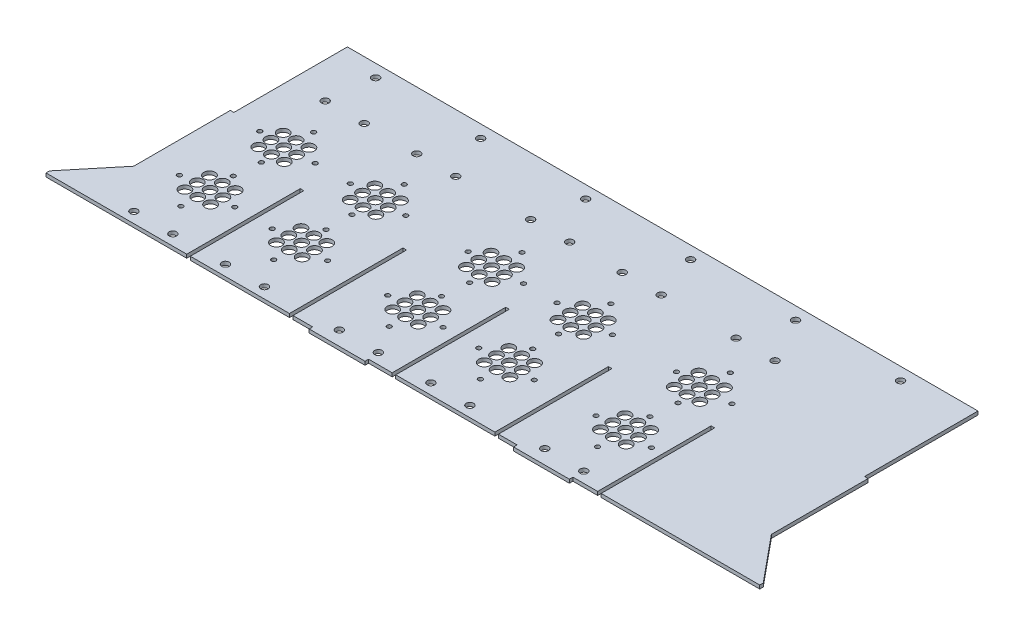
SolidWorks part; units mm, degrees
material "6061-T6 (SS)"
ref_plane "X-Y Datum" through (0, 0, 0) normal (0, 0, 1) x (1, 0, 0)
ref_plane "X-Z Datum" through (0, 0, 0) normal (0, 1, 0) x (1, 0, 0)
ref_plane "Y-Z Datum" through (0, 0, 0) normal (1, 0, 0) x (0, 0, -1)
sketch "Sketch1" plane through (0, 0, 0) normal (0, 0, 1) x (1, 0, 0)
  line L1 (-285.4305, -1.5875) -> (285.4305, -1.5875)
  line L2 (-285.4305, -1.5875) -> (-285.4305, 1.5875)
  line L3 (-285.4305, 1.5875) -> (285.4305, 1.5875)
  line L4 (285.4305, -1.5875) -> (285.4305, 1.5875)
  line L5 (-285.4305, -1.5875) -> (285.4305, 1.5875) construction
  line L6 (-285.4305, 1.5875) -> (285.4305, -1.5875) construction
  point P0 (0, 0)
  dimension "D1" = 570.861
  dimension "D2" = 3.175
extrude "Boss-Extrude1" add sketch "Sketch1" along normal blind 232.6
sketch "Sketch2" plane through (0, 1.5875, 0) normal (0, 1, 0) x (1, 0, 0)
  line L0 (-176.5505, -181.8) -> (-285.4305, -181.8) construction
  line L1 (-285.4305, -232.6) -> (-285.4305, 0) construction
  line L3 (285.4305, -232.6) -> (-285.4305, -232.6) construction
  line L4 (-178.0615, -232.6) -> (-174.8865, -232.6)
  line L6 (-178.0615, -118.3) -> (-174.8865, -118.3)
  line L8 (-178.0615, -232.6) -> (-174.8865, -232.6)
  line L9 (-178.0615, -232.6) -> (-178.0615, -118.3)
  line L10 (-178.0615, -118.3) -> (-174.8865, -118.3)
  line L11 (-174.8865, -232.6) -> (-174.8865, -118.3)
  line L17 (-178.0615, -118.3) -> (-174.8865, -118.3)
  line L38 (-285.4305, 0) -> (-282.2555, 0)
  line L39 (-285.4305, 0) -> (-285.4305, -101.6)
  line L40 (-285.4305, -101.6) -> (-282.2555, -101.6)
  line L41 (-282.2555, 0) -> (-282.2555, -101.6)
  line L42 (285.4305, 0) -> (282.2555, 0)
  line L43 (285.4305, 0) -> (285.4305, -101.6)
  line L44 (285.4305, -101.6) -> (282.2555, -101.6)
  line L45 (282.2555, 0) -> (282.2555, -101.6)
  line M3 (285.4305, 0) -> (-285.4305, 0)
  line M4 (-285.4305, 0) -> (-285.4305, -232.6)
  line M6 (285.4305, -232.6) -> (285.4305, 0)
  dimension "D2" = 50.8
  dimension "D3" = 3.175
  dimension "D6" = 3.175
  dimension "D7" = 101.6
  dimension "D4" = 114.3
  dimension "D8" = 3.175
  dimension "D9" = 101.6
sketch "Sketch6" plane through (0, 0, 232.6) normal (0, 0, 1) x (1, 0, 0)
  line L0 (285.4305, 1.5875) -> (-285.4305, 1.5875) construction
  line L1 (-285.4305, 1.5875) -> (-285.4305, -1.5875) construction
  line L14 (152.263, -1.5875) -> (152.263, 1.5875)
  line L15 (102.263, 1.5875) -> (152.263, 1.5875)
  line L16 (102.263, -1.5875) -> (152.263, 1.5875) construction
  line L17 (102.263, 1.5875) -> (152.263, -1.5875) construction
  line L18 (102.263, -1.5875) -> (152.263, -1.5875)
  line L19 (102.263, -1.5875) -> (102.263, 1.5875)
  line L20 (-30.6951, -1.5875) -> (-30.6951, 1.5875)
  line L21 (-80.6951, 1.5875) -> (-30.6951, 1.5875)
  line L22 (-80.6951, -1.5875) -> (-30.6951, 1.5875) construction
  line L23 (-80.6951, 1.5875) -> (-30.6951, -1.5875) construction
  line L24 (-80.6951, -1.5875) -> (-30.6951, -1.5875)
  line L25 (-80.6951, -1.5875) -> (-80.6951, 1.5875)
  point P4 (-55.6951, 0)
  point P5 (127.263, 0)
  dimension "D1" = 3.175
  dimension "D2" = 50
  dimension "D3" = 3.175
  dimension "D4" = 229.7354
  dimension "D5" = 182.9581
sketch "Sketch7" plane through (0, -1.5875, 0) normal (0, -1, 0) x (-1, 0, 0)
  line L1 (-285.4305, -232.6) -> (-285.4305, 0) construction
  circle A2 centre (-224.2195, -11.2916) radius 3.302
  dimension "D1" = 61.211
  dimension "D2" = 6.604
extrude "Cut-Extrude4" cut sketch "Sketch7" against normal through all contours A2 region at (224.2195, -1.5875, 11.2916)
extrude "Boss-Extrude2" add sketch "Sketch6" along normal blind 3.175
pattern_linear "LPattern1" count 6 spacing 93.98 along (-1, 0, 0) of "Cut-Extrude4"
extrude "Cut-Extrude5" cut sketch "Sketch2" against normal through all contours L41 L40 M3 M4 | L45 L44 M3 M6 region at (283.843, 1.5875, 50.8) region at (-283.843, 1.5875, 50.8)
sketch "Sketch12" plane through (0, 1.5875, 0) normal (0, 1, 0) x (1, 0, 0)
  line L0 (-285.4305, -232.6) -> (-285.4305, -101.6) construction
  line L1 (-285.4305, -232.6) -> (-285.4305, -188.15)
  line L2 (285.4305, -232.6) -> (285.4305, -101.6) construction
  line L3 (285.4305, -232.6) -> (285.4305, -101.6)
  line L4 (-285.4305, -232.6) -> (-319.4665, -232.6)
  line L6 (-319.4665, -232.6) -> (-319.4665, -229.425)
  line L7 (-319.4665, -229.425) -> (-285.4305, -188.15)
  line M9 (-285.4305, -101.6) -> (-285.4305, -232.6)
  dimension "D1" = 34.036
  dimension "D2" = 44.45
  dimension "D3" = 3.175
extrude "Boss-Extrude3" add sketch "Sketch12" against normal blind 3.175 contours L4 M9 region at (-297.5322, 1.5875, 217.7128)
mirror "Mirror1" about plane through (0, 0, 0) normal (1, 0, 0) of "Boss-Extrude3"
sketch "Sketch13" plane through (0, -1.5875, 0) normal (0, -1, 0) x (1, 0, 0)
  line L0 (-193.4755, 232.6) -> (-193.4755, 131)
  line L1 (-319.4665, 232.6) -> (-80.6951, 232.6) construction
  line L2 (-282.2555, 0) -> (-282.2555, 101.6) construction
  line L3 (-193.4755, 232.6) -> (-190.3005, 232.6)
  line L5 (-193.4755, 232.6) -> (-193.4755, 131)
  line L6 (-193.4755, 131) -> (-190.3005, 131)
  line L7 (-190.3005, 232.6) -> (-190.3005, 131)
  line M23 (-80.6951, 232.6) -> (-319.4665, 232.6)
  dimension "D1" = 88.78
  dimension "D2" = 101.6
  dimension "D3" = 3.175
extrude "Cut-Extrude6" cut sketch "Sketch13" against normal through all contours L7 L0 L6 M23 region at (-191.888, -1.5875, 181.8)
pattern_linear "LPattern2" count 5 spacing 91.955 along (1, 0, 0) of "Cut-Extrude6"
sketch "Sketch14" plane through (0, 1.5875, 0) normal (0, 1, 0) x (1, 0, 0)
  circle A0 centre (-215.403, -51.825) radius 3 construction
  circle A1 centre (-250.328, -51.825) radius 3 construction
  circle A2 centre (-215.403, -223.075) radius 3 construction
  circle A3 centre (-250.328, -223.075) radius 3 construction
  circle A4 centre (-215.403, -51.825) radius 3 construction
  circle A5 centre (-250.328, -51.825) radius 3 construction
  circle A6 centre (-215.403, -223.075) radius 3 construction
  circle A7 centre (-250.328, -223.075) radius 3 construction
  circle A8 centre (-133.4455, -51.825) radius 3.3 construction
  circle A9 centre (-168.3705, -51.825) radius 3.3 construction
  circle A10 centre (-133.4455, -223.075) radius 3.3 construction
  circle A11 centre (-168.3705, -223.075) radius 3.3 construction
  circle A12 centre (-133.4455, -51.825) radius 3.3 construction
  circle A13 centre (-168.3705, -51.825) radius 3.3 construction
  circle A14 centre (-133.4455, -223.075) radius 3.3 construction
  circle A15 centre (-168.3705, -223.075) radius 3.3 construction
hole_wizard "M6 Clearance Hole1" positions "Sketch15" profile "Sketch16" hole size "M6" standard "ANSI Metric" end condition through all
sketch "Sketch15" plane through (0, 1.5875, 0) normal (0, 1, 0) x (1, 0, 0)
  point P0 (-250.328, -223.075)
  point P3 (-215.403, -223.075)
  point P6 (-215.403, -51.825)
  point P9 (-250.328, -51.825)
sketch "Sketch16" plane through (-250.328, 1.5875, 223.075) normal (1, 0, 0) x (0, 0, 1)
  line L0 (0, 0) -> (0, 3.175)
  line L1 (0, 3.175) -> (3.3, 3.175)
  line L2 (3.3, 3.175) -> (3.3, 0)
  line L5 (3.3, 0) -> (0, 0)
  line L11 (0, -6.35) -> (0, 107.95) construction
  dimension "Thru Hole Dia." = 6.6
  dimension "Thru Hole Depth" = 3.175
hole_wizard "M6 Clearance Hole2" positions "Sketch17" profile "Sketch18" hole size "M6" standard "ANSI Metric" end condition through all
sketch "Sketch17" plane through (0, 1.5875, 0) normal (0, 1, 0) x (1, 0, 0)
  point P0 (-168.3705, -223.075)
  point P3 (-133.4455, -223.075)
  point P6 (-168.3705, -51.825)
  point P9 (-133.4455, -51.825)
sketch "Sketch18" plane through (-168.3705, 1.5875, 223.075) normal (1, 0, 0) x (0, 0, 1)
  line L0 (0, 0) -> (0, 3.175)
  line L1 (0, 3.175) -> (3.3, 3.175)
  line L2 (3.3, 3.175) -> (3.3, 0)
  line L5 (3.3, 0) -> (0, 0)
  line L11 (0, -6.35) -> (0, 107.95) construction
  dimension "Thru Hole Dia." = 6.6
  dimension "Thru Hole Depth" = 3.175
pattern_linear "LPattern3" count 3 spacing 183.92 along (1, 0, 0) of "M6 Clearance Hole1"
pattern_linear "LPattern4" count 2 spacing 183.92 along (1, 0, 0) of "M6 Clearance Hole2"
sketch "Sketch20" plane through (0, 7.935, 0) normal (0, 1, 0) x (1, 0, 0)
  circle A0 centre (-206.4649, -104.6371) radius 2 construction
  circle A1 centre (-231.2504, -128.0582) radius 2 construction
  circle A2 centre (-256.0359, -104.6371) radius 2 construction
  circle A3 centre (-231.2504, -81.216) radius 2 construction
  circle A4 centre (-206.4649, -104.6371) radius 2
  circle A5 centre (-231.2504, -128.0582) radius 2
  circle A6 centre (-256.0359, -104.6371) radius 2
  circle A7 centre (-231.2504, -81.216) radius 2
  circle A8 centre (-174.9826, -174.6221) radius 2 construction
  circle A9 centre (-150.197, -198.0432) radius 2 construction
  circle A10 centre (-150.197, -151.201) radius 2 construction
  circle A11 centre (-125.4115, -174.6221) radius 2 construction
  circle A12 centre (-21.9991, -174.6221) radius 2 construction
  circle A13 centre (-46.7846, -198.0432) radius 2 construction
  circle A14 centre (-46.7846, -151.201) radius 2 construction
  circle A15 centre (-71.5702, -174.6221) radius 2 construction
  circle A16 centre (-174.9826, -174.6221) radius 2
  circle A17 centre (-150.197, -198.0432) radius 2
  circle A18 centre (-150.197, -151.201) radius 2
  circle A19 centre (-125.4115, -174.6221) radius 2
  circle A20 centre (-21.9991, -174.6221) radius 2
  circle A21 centre (-46.7846, -198.0432) radius 2
  circle A22 centre (-46.7846, -151.201) radius 2
  circle A23 centre (-71.5702, -174.6221) radius 2
  circle A24 centre (-125.4115, -104.6371) radius 2 construction
  circle A25 centre (-150.197, -128.0582) radius 2 construction
  circle A26 centre (-174.9826, -104.6371) radius 2 construction
  circle A27 centre (-150.197, -81.216) radius 2 construction
  circle A28 centre (-208.4991, -174.6221) radius 2 construction
  circle A29 centre (-233.2846, -198.0432) radius 2 construction
  circle A30 centre (-258.0702, -174.6221) radius 2 construction
  circle A31 centre (-233.2846, -151.201) radius 2 construction
  circle A32 centre (-125.4115, -104.6371) radius 2
  circle A33 centre (-150.197, -128.0582) radius 2
  circle A34 centre (-174.9826, -104.6371) radius 2
  circle A35 centre (-150.197, -81.216) radius 2
  circle A36 centre (-208.4991, -174.6221) radius 2
  circle A37 centre (-233.2846, -198.0432) radius 2
  circle A38 centre (-258.0702, -174.6221) radius 2
  circle A39 centre (-233.2846, -151.201) radius 2
  circle A40 centre (-44.7504, -128.0582) radius 2 construction
  circle A41 centre (-19.9649, -104.6371) radius 2 construction
  circle A42 centre (-44.7504, -81.216) radius 2 construction
  circle A43 centre (-69.5359, -104.6371) radius 2 construction
  circle A44 centre (-44.7504, -128.0582) radius 2
  circle A45 centre (-19.9649, -104.6371) radius 2
  circle A46 centre (-44.7504, -81.216) radius 2
  circle A47 centre (-69.5359, -104.6371) radius 2
  circle A48 centre (34.803, -198.0432) radius 2 construction
  circle A49 centre (59.5885, -174.6221) radius 2 construction
  circle A50 centre (34.803, -151.201) radius 2 construction
  circle A51 centre (10.0174, -174.6221) radius 2 construction
  circle A52 centre (34.803, -128.0582) radius 2 construction
  circle A53 centre (10.0174, -104.6371) radius 2 construction
  circle A54 centre (59.5885, -104.6371) radius 2 construction
  circle A55 centre (34.803, -81.216) radius 2 construction
  circle A56 centre (34.803, -198.0432) radius 2
  circle A57 centre (59.5885, -174.6221) radius 2
  circle A58 centre (34.803, -151.201) radius 2
  circle A59 centre (10.0174, -174.6221) radius 2
  circle A60 centre (34.803, -128.0582) radius 2
  circle A61 centre (10.0174, -104.6371) radius 2
  circle A62 centre (59.5885, -104.6371) radius 2
  circle A63 centre (34.803, -81.216) radius 2
  circle A64 centre (139.7154, -198.0432) radius 2 construction
  circle A65 centre (114.9298, -174.6221) radius 2 construction
  circle A66 centre (164.5009, -174.6221) radius 2 construction
  circle A67 centre (139.7154, -151.201) radius 2 construction
  circle A68 centre (166.5351, -104.6371) radius 2 construction
  circle A69 centre (141.7496, -128.0582) radius 2 construction
  circle A70 centre (116.9641, -104.6371) radius 2 construction
  circle A71 centre (141.7496, -81.216) radius 2 construction
  circle A72 centre (139.7154, -198.0432) radius 2
  circle A73 centre (114.9298, -174.6221) radius 2
  circle A74 centre (164.5009, -174.6221) radius 2
  circle A75 centre (139.7154, -151.201) radius 2
  circle A76 centre (166.5351, -104.6371) radius 2
  circle A77 centre (141.7496, -128.0582) radius 2
  circle A78 centre (116.9641, -104.6371) radius 2
  circle A79 centre (141.7496, -81.216) radius 2
extrude "Cut-Extrude8" cut sketch "Sketch20" against normal through all
sketch "Sketch21" plane through (0, 1.5875, 0) normal (0, 1, 0) x (1, 0, 0)
  circle A1 centre (-232.8655, -95.3433) radius 5 construction
  circle A2 centre (-244.3655, -95.3433) radius 5 construction
  circle A3 centre (-244.3655, -106.3433) radius 5 construction
  circle A4 centre (-244.3655, -117.3433) radius 5 construction
  circle A5 centre (-232.8655, -95.3433) radius 5
  circle A6 centre (-244.3655, -95.3433) radius 5
  circle A7 centre (-244.3655, -106.3433) radius 5
  circle A8 centre (-244.3655, -117.3433) radius 5
  circle A9 centre (-221.3655, -106.3433) radius 5 construction
  circle A10 centre (-232.8655, -106.3433) radius 5 construction
  circle A11 centre (-221.3655, -106.3433) radius 5
  circle A12 centre (-232.8655, -106.3433) radius 5
  circle A13 centre (-232.8655, -117.3433) radius 5 construction
  circle A14 centre (-221.3655, -117.3433) radius 5 construction
  circle A15 centre (-221.3655, -95.3433) radius 5 construction
  circle A16 centre (-232.8655, -117.3433) radius 5
  circle A17 centre (-221.3655, -117.3433) radius 5
  circle A18 centre (-221.3655, -95.3433) radius 5
  circle A37 centre (-244.3655, -183.3433) radius 5 construction
  circle A38 centre (-232.8655, -183.3433) radius 5 construction
  circle A39 centre (-221.3655, -183.3433) radius 5 construction
  circle A40 centre (-221.3655, -172.3433) radius 5 construction
  circle A41 centre (-221.3655, -161.3433) radius 5 construction
  circle A42 centre (-232.8655, -161.3433) radius 5 construction
  circle A43 centre (-232.8655, -172.3433) radius 5 construction
  circle A44 centre (-244.3655, -172.3433) radius 5 construction
  circle A45 centre (-244.3655, -161.3433) radius 5 construction
  circle A46 centre (-244.3655, -183.3433) radius 5
  circle A47 centre (-232.8655, -183.3433) radius 5
  circle A48 centre (-221.3655, -183.3433) radius 5
  circle A49 centre (-221.3655, -172.3433) radius 5
  circle A50 centre (-221.3655, -161.3433) radius 5
  circle A51 centre (-232.8655, -161.3433) radius 5
  circle A52 centre (-232.8655, -172.3433) radius 5
  circle A53 centre (-244.3655, -172.3433) radius 5
  circle A54 centre (-244.3655, -161.3433) radius 5
extrude "Cut-Extrude9" cut sketch "Sketch21" against normal through all
pattern_linear "LPattern5" count 3 spacing 186 along (1, 0, 0) of "Cut-Extrude9"
sketch "Sketch22" plane through (0, 1.5875, 0) normal (0, 1, 0) x (1, 0, 0)
  circle A0 centre (-139.408, -117.3433) radius 5 construction
  circle A1 centre (-150.908, -117.3433) radius 5 construction
  circle A2 centre (-162.408, -117.3433) radius 5 construction
  circle A3 centre (-162.408, -106.3433) radius 5 construction
  circle A4 centre (-150.908, -106.3433) radius 5 construction
  circle A5 centre (-139.408, -106.3433) radius 5 construction
  circle A6 centre (-139.408, -95.3433) radius 5 construction
  circle A7 centre (-150.908, -95.3433) radius 5 construction
  circle A8 centre (-162.408, -95.3433) radius 5 construction
  circle A9 centre (-139.408, -117.3433) radius 5
  circle A10 centre (-150.908, -117.3433) radius 5
  circle A11 centre (-162.408, -117.3433) radius 5
  circle A12 centre (-162.408, -106.3433) radius 5
  circle A13 centre (-150.908, -106.3433) radius 5
  circle A14 centre (-139.408, -106.3433) radius 5
  circle A15 centre (-139.408, -95.3433) radius 5
  circle A16 centre (-150.908, -95.3433) radius 5
  circle A17 centre (-162.408, -95.3433) radius 5
  circle A18 centre (-139.408, -183.3433) radius 5 construction
  circle A19 centre (-139.408, -172.3433) radius 5 construction
  circle A20 centre (-139.408, -161.3433) radius 5 construction
  circle A21 centre (-150.908, -161.3433) radius 5 construction
  circle A22 centre (-150.908, -172.3433) radius 5 construction
  circle A23 centre (-150.908, -183.3433) radius 5 construction
  circle A24 centre (-162.408, -183.3433) radius 5 construction
  circle A25 centre (-162.408, -172.3433) radius 5 construction
  circle A26 centre (-162.408, -161.3433) radius 5 construction
  circle A27 centre (-139.408, -183.3433) radius 5
  circle A28 centre (-139.408, -172.3433) radius 5
  circle A29 centre (-139.408, -161.3433) radius 5
  circle A30 centre (-150.908, -161.3433) radius 5
  circle A31 centre (-150.908, -172.3433) radius 5
  circle A32 centre (-150.908, -183.3433) radius 5
  circle A33 centre (-162.408, -183.3433) radius 5
  circle A34 centre (-162.408, -172.3433) radius 5
  circle A35 centre (-162.408, -161.3433) radius 5
extrude "Cut-Extrude10" cut sketch "Sketch22" against normal through all
pattern_linear "LPattern6" count 2 spacing 186 along (1, 0, 0) of "Cut-Extrude10"
